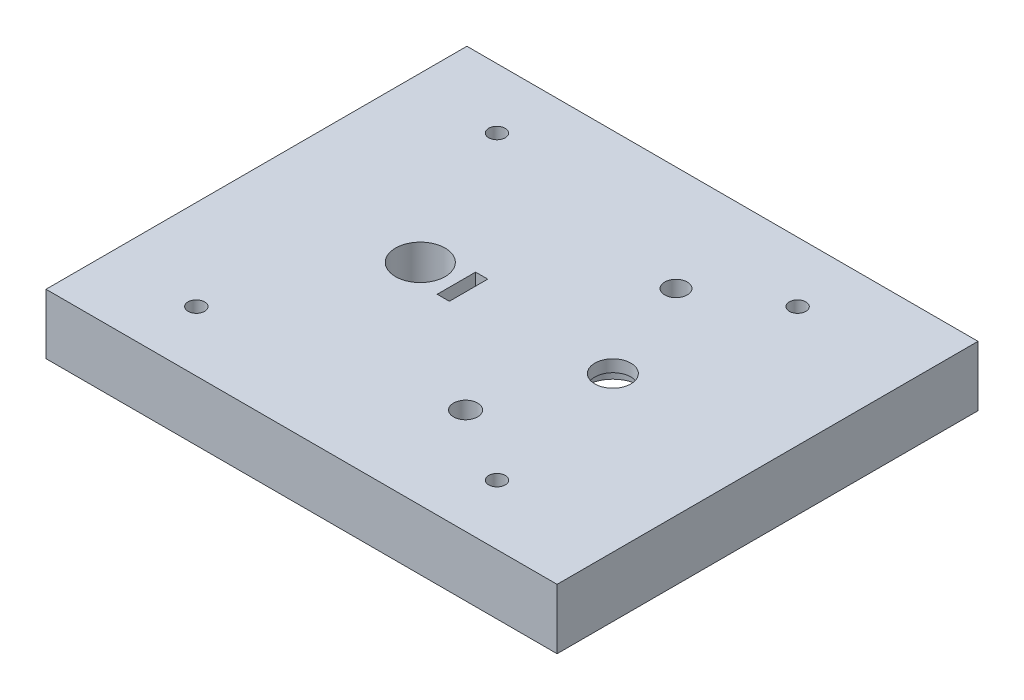
SolidWorks part; units mm, degrees
ref_plane "Front Plane" through (0, 0, 0) normal (0, 0, 1) x (1, 0, 0)
ref_plane "Top Plane" through (0, 0, 0) normal (0, 1, 0) x (1, 0, 0)
ref_plane "Right Plane" through (0, 0, 0) normal (1, 0, 0) x (0, 0, -1)
sketch "Sketch1" plane through (0, 0, 0) normal (0, 1, 0) x (1, 0, 0)
  line L1 (-52.2759, 35) -> (32.7241, 35)
  line L2 (-52.2759, 35) -> (-52.2759, -35)
  line L3 (-52.2759, -35) -> (32.7241, -35)
  line L4 (32.7241, 35) -> (32.7241, -35)
  line L11 (5.5, 2.0001) -> (5.5, -1.9999)
  line L13 (8.5, 2.0001) -> (8.5, -1.9999)
  line L16 (3.625, 17.5) -> (3.625, 13.7295)
  line L17 (-3.625, 17.5) -> (-3.625, 13.7295)
  line L18 (3.625, -17.5) -> (3.625, -13.7295)
  line L19 (-3.625, -17.5) -> (-3.625, -13.7295)
  line L20 (-17, -7) -> (-17, 7)
  line L21 (-17, -7) -> (-12.3548, -7)
  line L22 (-17, 7) -> (-12.3548, 7)
  line L24 (-19.0247, -3.193) -> (-19.0247, 3.193)
  line L25 (-19.0247, 3.193) -> (-17, 3.193)
  line L33 (-19.0247, -3.193) -> (-17, -3.193)
  circle A0 centre (-37.2759, 25) radius 1.375
  circle A1 centre (12.7241, 25) radius 1.375
  circle A2 centre (12.7241, -25) radius 1.375
  circle A3 centre (-37.2759, -25) radius 1.375
  arc A6 (5.5, 2.0001) -> (8.5, 2.0001) centre (7, 0) cw
  arc A7 (5.5, -1.9999) -> (8.5, -1.9999) centre (7, 0) ccw
  circle A8 centre (7, 0) radius 4.5
  circle A12 centre (-25.0247, 0) radius 4.125
  circle A13 centre (7, 0) radius 3
  arc A14 (-3.625, 13.7295) -> (-12.3548, 7) centre (0, 0) ccw
  circle A17 centre (85.0307, -10.8481) radius 14
  circle A18 centre (86.1334, -28.3481) radius 2
  circle A19 centre (86.1334, 6.6519) radius 2
  arc A20 (-3.625, 13.7295) -> (-12.3548, 7) centre (0, 0) ccw
  circle A21 centre (0, 17.5) radius 1.875
  circle A22 centre (0, -17.5) radius 2
  arc A23 (3.625, 17.5) -> (-3.625, 17.5) centre (0, 17.5) ccw
  arc A24 (-3.625, -17.5) -> (3.625, -17.5) centre (0, -17.5) ccw
  arc A26 (3.625, -13.7295) -> (3.625, 13.7295) centre (0, 0) ccw
  arc A27 (3.625, -13.7295) -> (3.625, 13.7295) centre (0, 0) ccw
  arc A28 (-12.3548, -7) -> (-3.625, -13.7295) centre (0, 0) ccw
  arc A29 (-12.3548, -7) -> (-3.625, -13.7295) centre (0, 0) ccw
  point P11 (-19.0247, 0)
  point P20 (-17, 0)
  point P68 (3.625, 15.6148)
  dimension "D3" = 15
  dimension "D6" = 2.75
  dimension "D7" = 17
  dimension "D10" = 4.6452
  dimension "D11" = 9
  dimension "D12" = 35
  dimension "D13" = 3.75
  dimension "D14" = 6.386
  dimension "D15" = 1.1027
  dimension "D17" = 1.1027
  dimension "D20" = 8.25
  dimension "D21" = 6
  dimension "D16" = 14
  dimension "D25" = 14.2
  dimension "D1" = 85
  dimension "D2" = 70
  dimension "D4" = 10
  dimension "D8" = 4
  dimension "D9" = 3
  dimension "D18" = 2.0247
  dimension "D19" = 4
  dimension "D22" = 32.7241
  dimension "D23" = 6
  dimension "D24" = 7
  dimension "D26" = 35
  dimension "D27" = 17.5
  dimension "D28" = 50
  dimension "D29" = 50
  dimension "D31" = 7.25
  dimension "D32" = 7.25
  dimension "D5" = 2
extrude "Boss-Extrude4" add sketch "Sketch1" along normal blind 10 contours L4 L1 L2 L3 A14 A2 A1 A0 A3 | A14 | A14 | A14 | A14 | A14 A8 | A8 A13 | A14 | L16 A23 L17 A14 A20 A21 | L19 A24 L18 A14 A22 region at (-9.7759, 0, -33.8989) region at (-1.7092, 0, -0.0389) region at (2.6273, 0, 0)
extrude "Cut-Extrude2" cut sketch "Sketch1<7>" along normal blind 6 contours L24 L33 L20 L25 | L21 A28 L19 A24 L18 A26 L16 A23 L17 A14 L22 L20 A8 A21 A22 region at (-1.7092, 0, -0.0389) region at (-18.0123, 0, 0)
sketch "Sketch1<7>" plane through (0, 0, 0) normal (0, 1, 0) x (1, 0, 0) same geometry as "Sketch1"
extrude "Cut-Extrude10" cut sketch "Sketch1<11>" along normal blind 8 contours A8 A13 region at (2.6273, 0, 0)
sketch "Sketch1<11>" plane through (0, 0, 0) normal (0, 1, 0) x (1, 0, 0) same geometry as "Sketch1"
